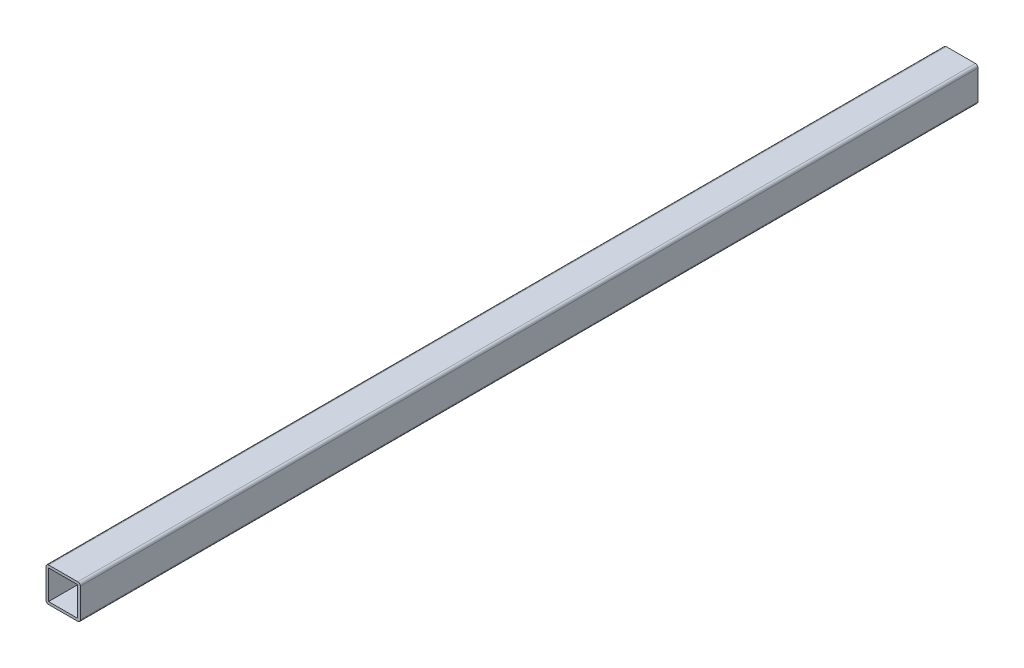
SolidWorks part; units mm, degrees
ref_plane "Front Plane" through (0, 0, 0) normal (0, 0, 1) x (1, 0, 0)
ref_plane "Top Plane" through (0, 0, 0) normal (0, 1, 0) x (1, 0, 0)
ref_plane "Right Plane" through (0, 0, 0) normal (1, 0, 0) x (0, 0, -1)
sketch "Sketch1" plane through (0, 0, 0) normal (0, 0, 1) x (1, 0, 0)
  line L1 (-610, 610) -> (-570, 610)
  line L2 (-610, 610) -> (-610, 570)
  line L3 (-610, 570) -> (-570, 570)
  line L4 (-570, 610) -> (-570, 570)
extrude "Boss-Extrude1" add sketch "Sketch1" along normal up to surface (1047 mm away)
fillet "Fillet1" radius 3 4 edges at (-570, 570, 523.5) (-570, 610, 523.5) (-610, 570, 523.5) (-610, 610, 523.5)
shell "Shell1" thickness 3 removed face at (-590, 590, 0) removed face at (-590, 590, 1047)
